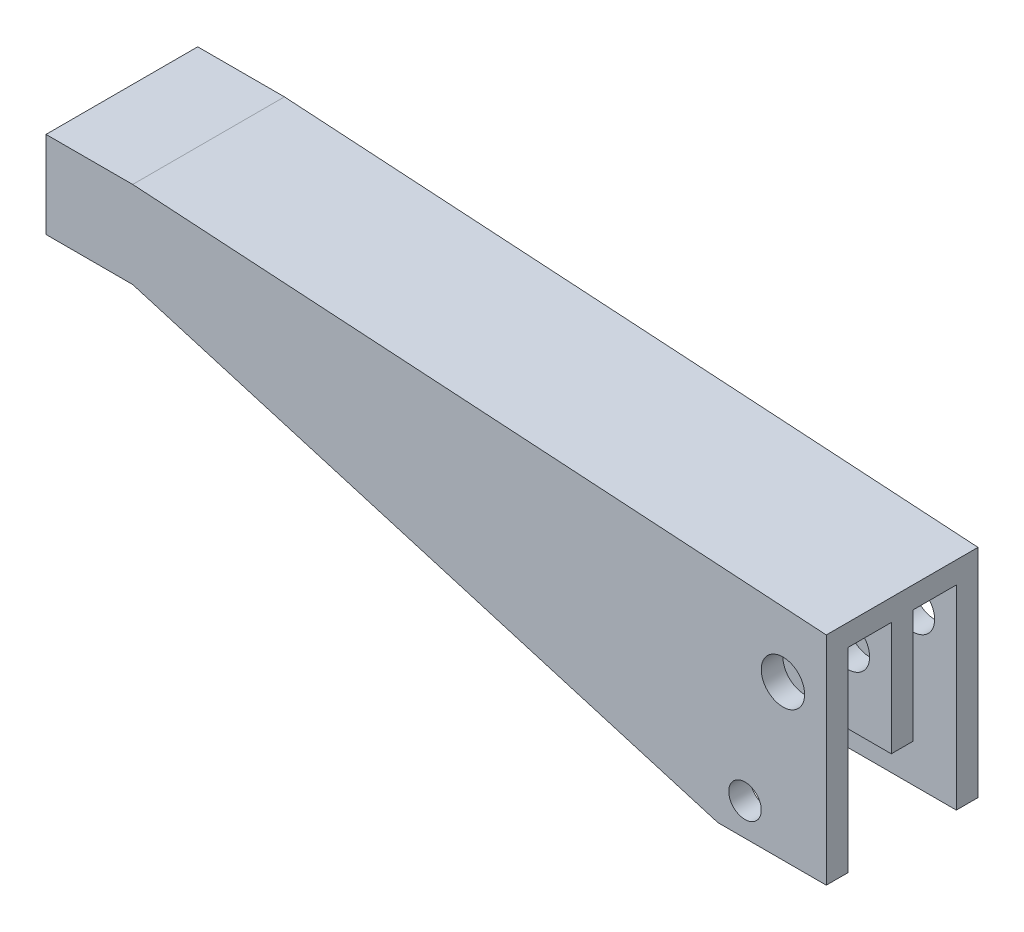
SolidWorks part; units mm, degrees
ref_plane "Front Plane" through (0, 0, 0) normal (0, 0, 1) x (1, 0, 0)
ref_plane "Top Plane" through (0, 0, 0) normal (0, 1, 0) x (1, 0, 0)
ref_plane "Right Plane" through (0, 0, 0) normal (1, 0, 0) x (0, 0, -1)
sketch "Sketch1" plane through (0, 0, 0) normal (0, 0, 1) x (1, 0, 0)
  line L0 (-914.4, 304.8) -> (-812.8, 304.8)
  line L1 (-914.4, 304.8) -> (-914.4, 203.2)
  line L2 (-914.4, 203.2) -> (-812.8, 203.2)
  line L4 (-127, 0) -> (0, 0)
  line L5 (0, 0) -> (0, 254)
  line L6 (0, 254) -> (-812.8, 304.8)
  line L7 (-812.8, 203.2) -> (-127, 0)
  point P6 (-137.0568, 0)
  dimension "D1" = 101.6
  dimension "D2" = 101.6
  dimension "D3" = 914.4
  dimension "D4" = 127
  dimension "D6" = 203.2
  dimension "D7" = 254
extrude "Boss-Extrude1" add sketch "Sketch1" against normal blind 25.4
ref_plane "Plane1" through (0, 0, 127) normal (0, 0, 1) x (1, 0, 0)
sketch "Sketch2" plane through (0, 0, 127) normal (0, 0, 1) x (1, 0, 0)
  line L8 (-812.8, 203.2) -> (-127, 0)
  line L10 (-127, 0) -> (0, 0)
  line L11 (0, 0) -> (0, 254)
  line L12 (0, 254) -> (-812.8, 304.8)
  line L13 (-812.8, 304.8) -> (-914.4, 304.8)
  line L14 (-914.4, 304.8) -> (-914.4, 203.2)
  line L15 (-914.4, 203.2) -> (-812.8, 203.2)
  line L16 (-812.8, 203.2) -> (-127, 0)
  line L18 (-127, 0) -> (0, 0)
  line L19 (0, 0) -> (0, 254)
  line L20 (0, 254) -> (-812.8, 304.8)
  line L21 (-812.8, 304.8) -> (-914.4, 304.8)
  line L22 (-914.4, 304.8) -> (-914.4, 203.2)
  line L23 (-914.4, 203.2) -> (-812.8, 203.2)
  dimension "D1" = 0
extrude "Boss-Extrude2" add sketch "Sketch2" along normal blind 25.4 separate body
sketch "Sketch3" plane through (0, 0, 152.4) normal (0, 0, 1) x (1, 0, 0)
  line L6 (-914.4, 279.4) -> (-914.4, 304.8)
  line L7 (-914.4, 304.8) -> (-812.8, 304.8)
  line L8 (-812.8, 304.8) -> (0, 254)
  line L9 (-25.4, 0) -> (-25.4, 230.1379)
  line L10 (-25.4, 230.1379) -> (-813.593, 279.4)
  line L11 (-813.593, 279.4) -> (-914.4, 279.4)
  line L12 (-25.4, 230.1379) -> (0, 228.5504)
  line L13 (-25.4, 230.1379) -> (-813.593, 279.4)
  line L14 (-813.593, 279.4) -> (-914.4, 279.4)
  line L15 (0, 0) -> (0, 254) construction
  line L16 (0, 228.5504) -> (0, 254)
  dimension "D1" = 25.4
extrude "Boss-Extrude3" add sketch "Sketch3" against normal up to surface (152.4 mm away) up to face at (-511.6286, 181.4286, 0)
ref_plane "Plane2" through (0, 0, 63.5) normal (0, 0, 1) x (1, 0, 0)
sketch "Sketch6" plane through (0, 0, 63.5) normal (0, 0, 1) x (1, 0, 0)
  line L8 (-812.8, 203.2) -> (-127, 0)
  line L10 (-127, 0) -> (0, 0)
  line L11 (0, 0) -> (0, 254)
  line L12 (0, 254) -> (-812.8, 304.8)
  line L13 (-812.8, 304.8) -> (-914.4, 304.8)
  line L14 (-914.4, 304.8) -> (-914.4, 203.2)
  line L15 (-914.4, 203.2) -> (-812.8, 203.2)
  line L16 (-812.8, 203.2) -> (-127, 0)
  line L18 (-127, 0) -> (0, 0)
  line L19 (0, 0) -> (0, 254)
  line L20 (0, 254) -> (-812.8, 304.8)
  line L21 (-812.8, 304.8) -> (-914.4, 304.8)
  line L22 (-914.4, 304.8) -> (-914.4, 203.2)
  line L23 (-914.4, 203.2) -> (-812.8, 203.2)
  dimension "D1" = 0
extrude "Boss-Extrude4" add sketch "Sketch6" along normal blind 12.7 and the other way blind 12.7
sketch "Sketch5" plane through (0, 0, 152.4) normal (0, 0, 1) x (1, 0, 0)
  line L1 (0, 228.5504) -> (-813.593, 279.4) construction
  line L2 (-127, 0) -> (0, 0) construction
  line L3 (0, 0) -> (0, 254) construction
  circle A0 centre (-50.8, 180.8759) radius 25.4
  circle A1 centre (-95.25, 38.1) radius 19.05
  point P2 (-25.4, 180.8759)
  point P5 (-50.8, 206.2759)
  point P9 (-95.25, 19.05)
  point P10 (-114.3, 38.1)
  point P13 (-50.8, 185.2618)
  point P14 (0, 0)
  point P17 (0, 0)
  point P18 (0, 0)
  dimension "D1" = 25.4
  dimension "D3" = 50.8
  dimension "D6" = 38.1
  dimension "D2" = 25.4
  dimension "D4" = 19.05
  dimension "D5" = 95.25
extrude "Cut-Extrude1" cut sketch "Sketch5" against normal through all
sketch "Sketch7" plane through (0, 0, 76.2) normal (0, 0, 1) x (1, 0, 0)
  line L0 (-448.4688, 95.25) -> (0, 95.25)
  line L1 (0, 95.25) -> (0, 0)
  line L2 (0, 0) -> (-127, 0)
  line L3 (-127, 0) -> (0, 0) construction
  line L4 (0, 0) -> (0, 228.5504) construction
  line L5 (-812.8, 203.2) -> (-127, 0) construction
  line L6 (-448.4688, 95.25) -> (-127, 0)
  point P3 (-127, 0)
  point P9 (-108.7353, 0)
  dimension "D1" = 95.25
extrude "Cut-Extrude2" cut sketch "Sketch7" against normal up to surface (25.4 mm away) up to face at (-76.2, 38.1, 50.8)
